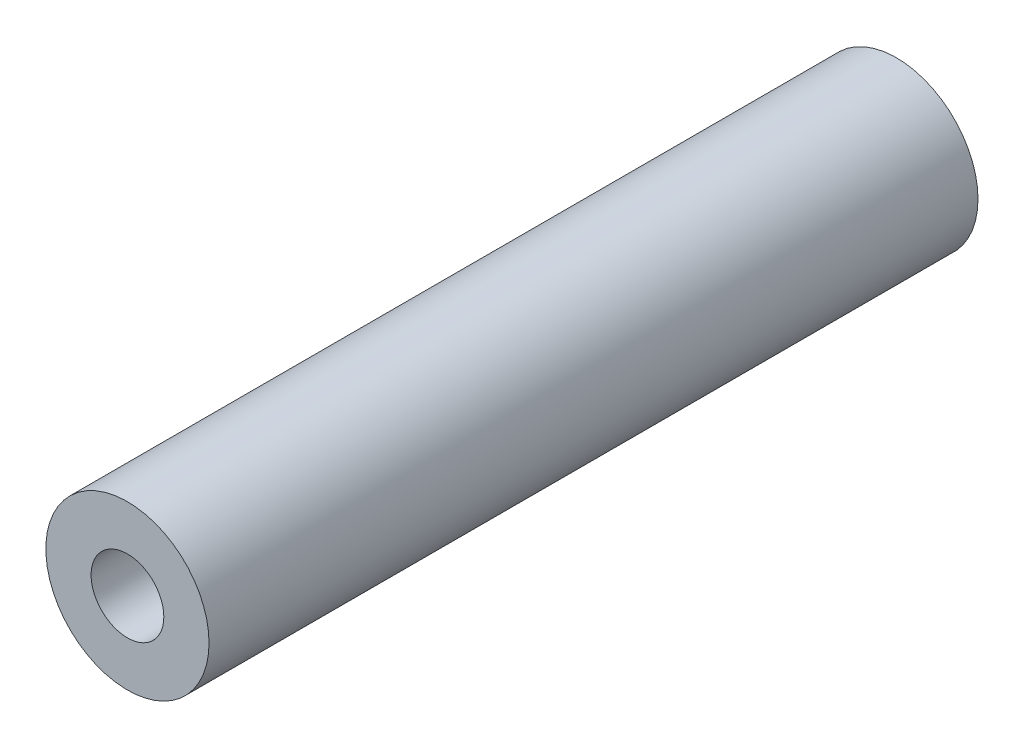
SolidWorks part; units mm, degrees
material "6061-T6 (SS)"
ref_plane "Front Plane" through (0, 0, 0) normal (0, 0, 1) x (1, 0, 0)
ref_plane "Top Plane" through (0, 0, 0) normal (0, 1, 0) x (1, 0, 0)
ref_plane "Right Plane" through (0, 0, 0) normal (1, 0, 0) x (0, 0, -1)
sketch "Sketch1" plane through (0, 0, 0) normal (0, 0, 1) x (1, 0, 0)
  circle A0 centre (0, 0) radius 2.5527
  circle A1 centre (0, 0) radius 5.7277
  dimension "D1" = 5.1054
  dimension "D2" = 3.175
extrude "Boss-Extrude1" add sketch "Sketch1" along normal blind 53.975
